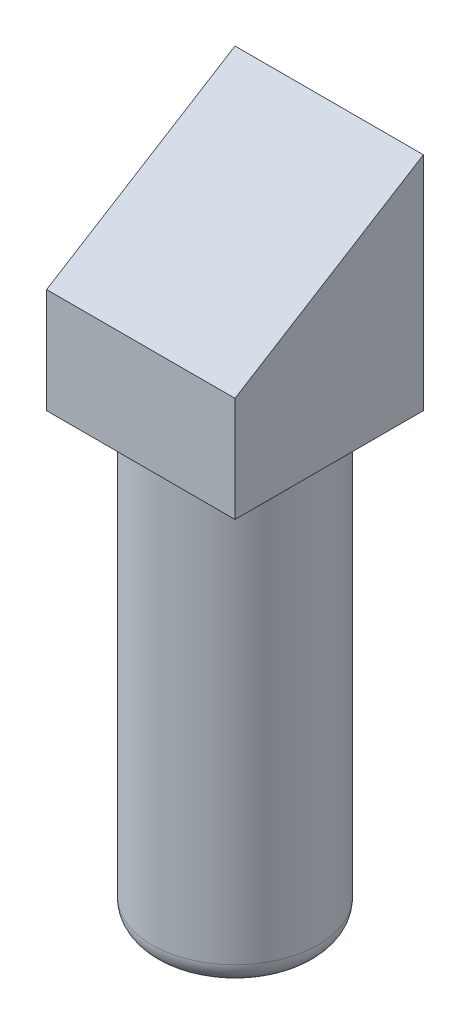
SolidWorks part; units mm, degrees
ref_plane "Front Plane" through (0, 0, 0) normal (0, 0, 1) x (1, 0, 0)
ref_plane "Top Plane" through (0, 0, 0) normal (0, 1, 0) x (1, 0, 0)
ref_plane "Right Plane" through (0, 0, 0) normal (1, 0, 0) x (0, 0, -1)
sketch "Sketch1" plane through (0, 0, 0) normal (0, 1, 0) x (1, 0, 0)
  circle A0 centre (0, 0) radius 2.5
  circle A1 centre (0, 0) radius 3.75
  dimension "D1" = 5
  dimension "D2" = 7.5
extrude "Boss-Extrude1" add sketch "Sketch1" along normal blind 20 contours A1
sketch "Sketch2" plane through (0, 0, 0) normal (0, -1, 0) x (1, 0, 0)
  circle A0 centre (0, 0) radius 2.5
  dimension "D1" = 5
extrude "Cut-Extrude1" cut sketch "Sketch2" against normal blind 20
sketch "Sketch5" plane through (0, 20, 0) normal (0, 1, 0) x (1, 0, 0)
  line L1 (-4.25, -4.25) -> (4.25, -4.25)
  line L2 (-4.25, -4.25) -> (-4.25, 4.25)
  line L3 (-4.25, 4.25) -> (4.25, 4.25)
  line L4 (4.25, -4.25) -> (4.25, 4.25)
  line L5 (-4.25, -4.25) -> (4.25, 4.25) construction
  line L6 (-4.25, 4.25) -> (4.25, -4.25) construction
  point P0 (0, 0)
  dimension "D1" = 8.5
  dimension "D2" = 8.5
extrude "Boss-Extrude3" add sketch "Sketch5" along normal blind 10
sketch "Sketch19" plane through (-4.25, 0, 0) normal (-1, 0, 0) x (0, 0, 1)
  line L0 (-4.25, 30) -> (4.25, 30)
  line L1 (4.25, 30) -> (4.25, 24.7322)
  line L2 (4.25, 30) -> (4.25, 20) construction
  line L3 (4.25, 24.7322) -> (-4.25, 30)
  dimension "D1" = 10
extrude "Cut-Extrude4" cut sketch "Sketch19" against normal blind 30
fillet "Fillet5" radius 1 1 edges at (0, 0, 3.75)
